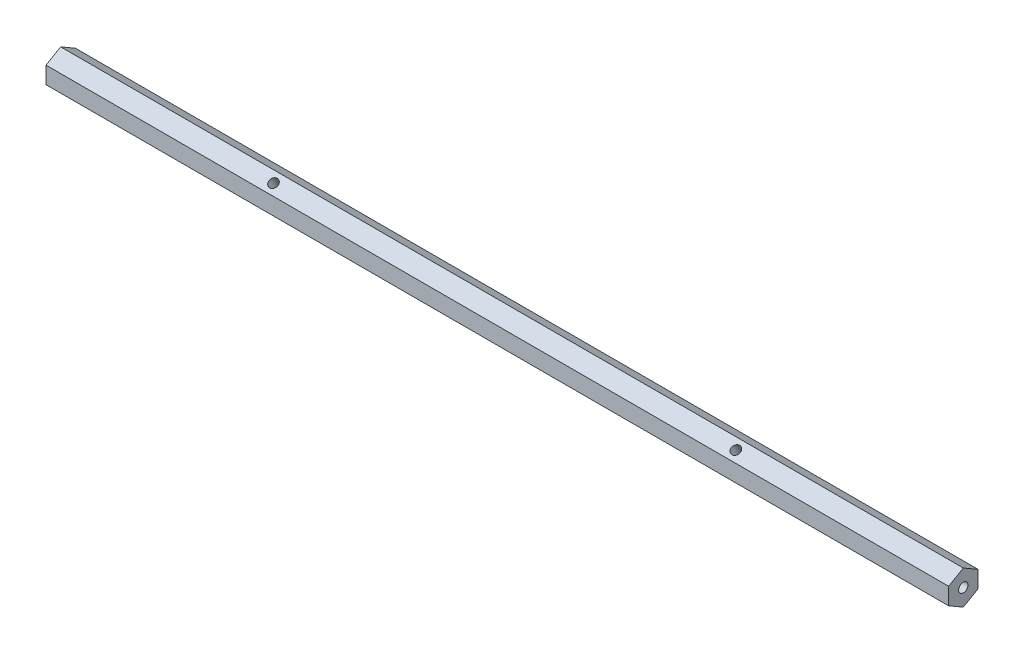
SolidWorks part; units mm, degrees
material "6061-T6 (SS)"
ref_plane "Front" through (0, 0, 0) normal (0, 0, 1) x (1, 0, 0)
ref_plane "Top" through (0, 0, 0) normal (0, 1, 0) x (1, 0, 0)
ref_plane "Right" through (0, 0, 0) normal (1, 0, 0) x (0, 0, -1)
ref_axis "Axis1" through (-80.9, 0, 0) along (1, 0, 0)
sketch "Sketch1" plane through (0, 0, 0) normal (1, 0, 0) x (0, 0, -1)
  line L1 (0, 7.3323) -> (-6.35, 3.6662)
  line L2 (-6.35, 3.6662) -> (-6.35, -3.6662)
  line L3 (-6.35, -3.6662) -> (0, -7.3323)
  line L4 (0, -7.3323) -> (6.35, -3.6662)
  line L5 (6.35, -3.6662) -> (6.35, 3.6662)
  line L6 (6.35, 3.6662) -> (0, 7.3323)
  circle A0 centre (0, 0) radius 6.35 construction
  dimension "D1" = 12.7
extrude "Boss-Extrude1" add sketch "Sketch1" along normal up to surface (390.525 mm away)
hole_wizard "#10-32 Tapped Hole1" positions "Sketch2" profile "Sketch3" tap size "#10-32" standard "ANSI Inch"
sketch "Sketch2" plane through (390.525, 0, 0) normal (1, 0, 0) x (0, 0, -1)
  point P0 (0, 0)
sketch "Sketch3" plane through (390.525, 0, 0) normal (0, 1, 0) x (0, 0, -1)
  line L0 (0, 0) -> (0, 13.2529)
  line L1 (0, 13.2529) -> (2.0193, 12.0396)
  line L2 (2.0193, 12.0396) -> (2.0193, 0)
  line L5 (2.0193, 0) -> (0, 0)
  line L10 (0, 13.2529) -> (-2.0193, 12.0396) construction
  line L11 (0, -6.35) -> (0, 107.95) construction
  dimension "Tap Drill Dia." = 4.0386
  dimension "Tap Drill Depth" = 12.0396
  dimension "Drill Angle" = 118
cosmetic thread "Hole Thread1" parameters "D1"=9.652, "D2"=4.826
hole_wizard "#10-32 Tapped Hole2" positions "Sketch4" profile "Sketch5" tap size "#10-32" standard "ANSI Inch"
sketch "Sketch4" plane through (0, 0, 0) normal (-1, 0, 0) x (0, 0, 1)
  point P0 (0, 0)
sketch "Sketch5" plane through (0, 0, 0) normal (0, 1, 0) x (0, 0, 1)
  line L0 (0, 0) -> (0, 13.2529)
  line L1 (0, 13.2529) -> (2.0193, 12.0396)
  line L2 (2.0193, 12.0396) -> (2.0193, 0)
  line L5 (2.0193, 0) -> (0, 0)
  line L10 (0, 13.2529) -> (-2.0193, 12.0396) construction
  line L11 (0, -6.35) -> (0, 107.95) construction
  dimension "Tap Drill Dia." = 4.0386
  dimension "Tap Drill Depth" = 12.0396
  dimension "Drill Angle" = 118
cosmetic thread "Hole Thread2" parameters "D1"=9.652, "D2"=4.826
sketch "Sketch6" plane through (0, 5.4993, 3.175) normal (0, 0.866, 0.5) x (1, 0, 0)
  line L0 (0, 7.3323) -> (0, 3.6662) construction
  line L3 (0, 0) -> (95.25, 0) construction
  line L4 (0, 3.6662) -> (0, -3.6662) construction
  line L9 (295.275, 0) -> (390.525, 0) construction
  line L10 (390.525, -3.6662) -> (390.525, 3.6662) construction
  circle A0 centre (95.25, 0) radius 1.905
  circle A1 centre (295.275, 0) radius 1.905
  dimension "D1" = 3.81
  dimension "D2" = 95.25
extrude "Cut-Extrude1" cut sketch "Sketch6" against normal through all
